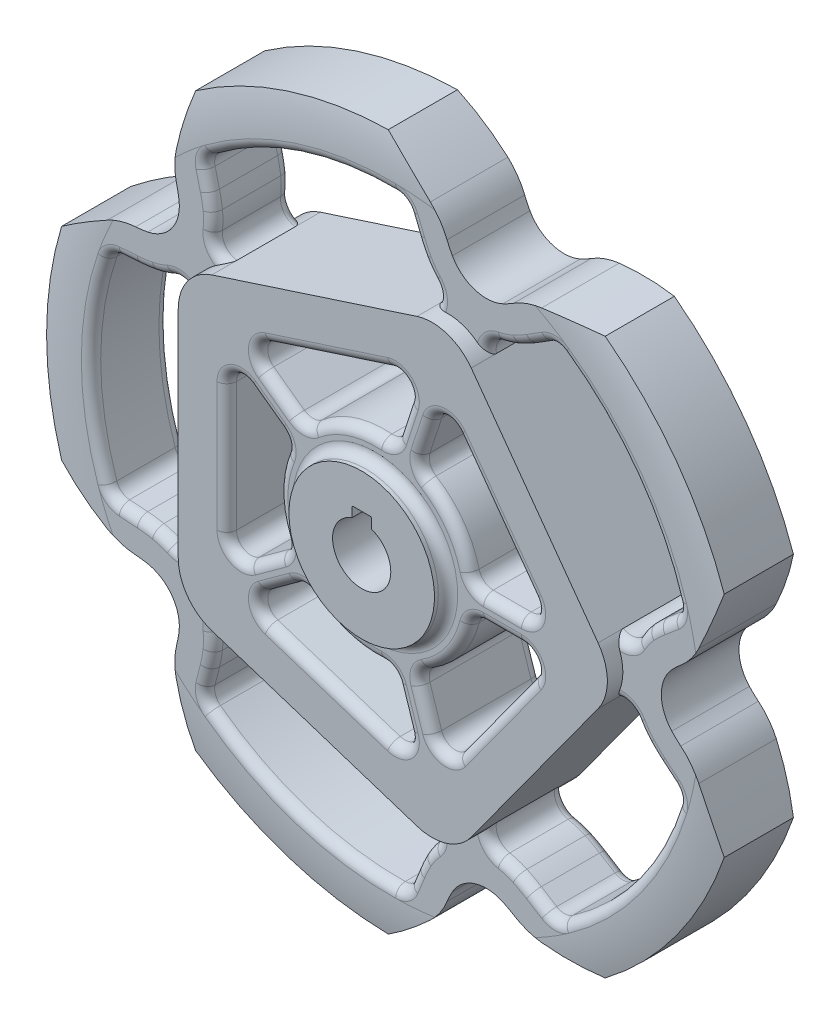
SolidWorks part; units mm, degrees
note: '?' marks a value the reader was unsure of.
material "7075-O (SS)"
ref_plane "Front Plane" through (0, 0, 0) normal (0, 0, 1) x (1, 0, 0)
ref_plane "Top Plane" through (0, 0, 0) normal (0, 1, 0) x (1, 0, 0)
ref_plane "Right Plane" through (0, 0, 0) normal (1, 0, 0) x (0, 0, -1)
sketch "Sketch1" plane through (0, 0, 0) normal (0, 0, 1) x (1, 0, 0)
  line L0 (0, 0) -> (71.6379, 52.048) construction
  line L1 (63.7988, 0) -> (19.7149, 60.6763) construction
  line L2 (19.7149, 60.6763) -> (-51.6143, 37.5) construction
  line L3 (-51.6143, 37.5) -> (-51.6143, -37.5) construction
  line L4 (-51.6143, -37.5) -> (19.7149, -60.6763) construction
  line L5 (19.7149, -60.6763) -> (63.7988, 0) construction
  line L6 (0, 0) -> (55.771, 0) construction
  circle A0 centre (0, 0) radius 63.7988 construction
  arc A1 (57.9284, 5.4759) -> (55.771, 0) centre (63.7988, 0) ccw
  arc A2 (59.7671, 7.2201) -> (57.9284, 5.4759) centre (73.1003, -8.6765) ccw
  arc A3 (59.7671, 7.2201) -> (63.4812, 12.0599) centre (50.7168, 18.0103) ccw
  arc A4 (63.4812, 12.0599) -> (71.6379, 52.048) centre (-15.9497, 49.0881) ccw
  circle A5 centre (0, 0) radius 81.3488 construction
  arc A6 (23.1088, 53.4011) -> (17.2342, 53.0413) centre (19.7149, 60.6763) cw
  arc A7 (25.3357, 54.6108) -> (23.1088, 53.4011) centre (14.3374, 72.2037) cw
  arc A8 (25.3357, 54.6108) -> (31.0865, 56.6475) centre (32.8012, 42.6691) cw
  arc A9 (31.0865, 56.6475) -> (71.6379, 52.048) centre (41.7569, -30.3381) cw
  arc A10 (57.9284, -5.4759) -> (55.771, 0) centre (63.7988, 0) cw
  arc A11 (59.7671, -7.2201) -> (57.9284, -5.4759) centre (73.1003, 8.6765) cw
  arc A12 (59.7671, -7.2201) -> (63.4812, -12.0599) centre (50.7168, -18.0103) cw
  arc A13 (63.4812, -12.0599) -> (71.6379, -52.048) centre (-15.9497, -49.0881) cw
  arc A14 (31.0865, -56.6475) -> (71.6379, -52.048) centre (41.7569, 30.3381) ccw
  arc A15 (25.3357, -54.6108) -> (31.0865, -56.6475) centre (32.8012, -42.6691) ccw
  arc A16 (25.3357, -54.6108) -> (23.1088, -53.4011) centre (14.3374, -72.2037) ccw
  arc A17 (23.1088, -53.4011) -> (17.2342, -53.0413) centre (19.7149, -60.6763) ccw
  arc A18 (12.693, -56.7854) -> (17.2342, -53.0413) centre (19.7149, -60.6763) cw
  arc A19 (11.6024, -59.073) -> (12.693, -56.7854) centre (30.841, -66.8413) cw
  arc A20 (11.6024, -59.073) -> (8.1471, -64.1009) centre (-1.4565, -53.8) cw
  arc A21 (8.1471, -64.1009) -> (-27.3633, -84.2155) centre (-51.6143, 0) cw
  arc A22 (-44.2687, -47.07) -> (-27.3633, -84.2155) centre (41.7569, -30.3381) ccw
  arc A23 (-44.1087, -40.9714) -> (-44.2687, -47.07) centre (-30.4446, -44.3812) ccw
  arc A24 (-44.1087, -40.9714) -> (-43.6465, -38.4796) centre (-64.2393, -35.9479) ccw
  arc A25 (-43.6465, -38.4796) -> (-45.1196, -32.7813) centre (-51.6143, -37.5) ccw
  arc A26 (-50.0837, -29.6194) -> (-45.1196, -32.7813) centre (-51.6143, -37.5) cw
  arc A27 (-52.5964, -29.2891) -> (-50.0837, -29.6194) centre (-54.0395, -49.9867) cw
  arc A28 (-52.5964, -29.2891) -> (-58.446, -27.5566) centre (-51.6169, -15.2399) cw
  arc A29 (-58.446, -27.5566) -> (-88.5494, 0) centre (-15.9497, 49.0881) cw
  arc A30 (-58.446, 27.5566) -> (-88.5494, 0) centre (-15.9497, -49.0881) ccw
  arc A31 (-52.5964, 29.2891) -> (-58.446, 27.5566) centre (-51.6169, 15.2399) ccw
  arc A32 (-52.5964, 29.2891) -> (-50.0837, 29.6194) centre (-54.0395, 49.9867) ccw
  arc A33 (-50.0837, 29.6194) -> (-45.1196, 32.7813) centre (-51.6143, 37.5) ccw
  arc A34 (-43.6465, 38.4796) -> (-45.1196, 32.7813) centre (-51.6143, 37.5) cw
  arc A35 (-44.1087, 40.9714) -> (-43.6465, 38.4796) centre (-64.2393, 35.9479) cw
  arc A36 (-44.1087, 40.9714) -> (-44.2687, 47.07) centre (-30.4446, 44.3812) cw
  arc A37 (-44.2687, 47.07) -> (-27.3633, 84.2155) centre (41.7569, 30.3381) cw
  arc A38 (8.1471, 64.1009) -> (-27.3633, 84.2155) centre (-51.6143, 0) ccw
  arc A39 (11.6024, 59.073) -> (8.1471, 64.1009) centre (-1.4565, 53.8) ccw
  arc A40 (11.6024, 59.073) -> (12.693, 56.7854) centre (30.841, 66.8413) ccw
  arc A41 (12.693, 56.7854) -> (17.2342, 53.0413) centre (19.7149, 60.6763) ccw
  point P9 (73.1003, -8.6765)
  point P12 (50.7168, 18.0103)
  point P97 (0, 0)
  dimension "D1" = 16.0557
  dimension "D4" = 162.6976
  dimension "D7" = 5
  dimension "D8" = 127.5976
  dimension "D2" = 8.6765
  dimension "D3" = 9.3015
  dimension "D5" = 13.082
  dimension "D6" = 18.0103
extrude "Boss-Extrude1" add sketch "Sketch1" along normal mid plane 16 contours A41 A40 A39 A38 A37 A36 A35 A34 A33 A32 A31 A30 A29 A28 A27 A26 A25 A24 A23 A22 A21 A20 A19 A18 A17 A16 A15 A14 A13 A12 A11 A10 A1 A2 A3 A4 A9 A8 A7 A6
sketch "Sketch2" plane through (0, 0, 0) normal (0, 0, 1) x (1, 0, 0)
  line L0 (19.7149, 60.6763) -> (0, 0) construction
  circle A0 centre (0, 0) radius 71.8266
  circle A1 centre (19.7149, 60.6763) radius 8.0278 construction
  dimension "D1" = 16.0557
extrude "Cut-Extrude1" cut sketch "Sketch2" along direction (0, 0, 1) on the side of the normal through all both and the other way through all flip side to cut
sketch "Sketch3" plane through (0, 0, 0) normal (0, 1, 0) x (1, 0, 0)
  line L0 (0, 0) -> (0, 8) construction
  line L1 (8.1471, 8) -> (-1.3828, 8) construction
  line L2 (0, 0) -> (-86.9505, 0) construction
  line L3 (0, 8) -> (-63.7988, 8) construction
  line L4 (-1.3828, 8) -> (-41.0921, 8) construction
  line L5 (-63.7988, 8) -> (-86.9505, 8)
  line L6 (-86.9505, 8) -> (-86.9505, -8)
  line L7 (-63.7988, -8) -> (-86.9505, -8)
  arc A0 (-63.7988, 8) -> (-86.9505, 0) centre (-63.7988, -29.5) ccw
  arc A1 (-63.7988, -8) -> (-86.9505, 0) centre (-63.7988, 29.5) cw
  dimension "D2" = 75
  dimension "D1" = 63.7988
revolve "Cut-Revolve1" cut sketch "Sketch3" angle 360 about L0
sketch "Sketch4" plane through (0, 0, 0) normal (0, 0, 1) x (1, 0, 0)
  line L1 (50.2029, 0) -> (15.5135, 47.7458)
  line L2 (15.5135, 47.7458) -> (-40.615, 29.5085)
  line L3 (-40.615, 29.5085) -> (-40.615, -29.5085)
  line L4 (-40.615, -29.5085) -> (15.5135, -47.7458)
  line L5 (15.5135, -47.7458) -> (50.2029, 0)
  circle A0 centre (0, 0) radius 40.615 construction
  dimension "D1" = 81.23
extrude "Boss-Extrude2" add sketch "Sketch4" along normal mid plane 22.4
fillet "Fillet2" radius 10 10 edges at (-40.615, 29.5085, 9.6) (-40.615, -29.5085, 9.6) (15.5135, -47.7458, 9.6) (50.2029, 0, 9.6) (15.5135, 47.7458, 9.6) (-40.615, 29.5085, -9.6) (15.5135, 47.7458, -9.6) (50.2029, 0, -9.6) (15.5135, -47.7458, -9.6) (-40.615, -29.5085, -9.6)
sketch "Sketch5" plane through (0, 0, 0) normal (0, 0, 1) x (1, 0, 0)
  circle A0 centre (0, 0) radius 15
  dimension "D1" = 30
extrude "Boss-Extrude3" add sketch "Sketch5" along normal blind 14
sketch "Sketch6" plane through (0, 0, 0) normal (0, 0, 1) x (1, 0, 0)
  line L5 (-2, 7.8) -> (2, 7.8)
  line L6 (-2, 7.8) -> (-2, 4.2)
  line L7 (-2, 4.2) -> (2, 4.2)
  line L8 (2, 7.8) -> (2, 4.2)
  line L9 (-2, 7.8) -> (2, 4.2) construction
  line L10 (-2, 4.2) -> (2, 7.8) construction
  circle A0 centre (0, 0) radius 6
  point P0 (0, 0)
  point P3 (0, 6)
  dimension "D1" = 12
  dimension "D2" = 4
  dimension "D3" = 3.6
extrude "Cut-Extrude2" cut sketch "Sketch6" against normal through all both and the other way through all contours L6 A0 L8 L7
fillet "Fillet10" radius 0.25 2 edges at (2, 7.8, 1.4) (-2, 7.8, 1.4)
sketch "Sketch7" plane through (0, 0, 0) normal (0, 0, 1) x (1, 0, 0)
  line L0 (19.7841, 41.8679) -> (45.9324, 5.8779)
  line L1 (45.9324, -5.8779) -> (19.7841, -41.8679)
  line L2 (8.6037, -45.5007) -> (-33.7052, -31.7537)
  line L4 (-33.7052, 31.7537) -> (8.6037, 45.5007) construction
  line L9 (-33.7052, 31.7537) -> (8.6037, 45.5007)
  line L10 (-12.5507, 38.6272) -> (-19.0969, 58.7742) construction
  line L11 (-40.615, -22.2431) -> (-40.615, 22.2431)
  arc A3 (8.6037, 45.5007) -> (8.7547, 50.3947) centre (6.2268, 48.0233) ccw
  arc A4 (8.7547, 50.3947) -> (6.5701, 53.3927) centre (19.7149, 60.6763) cw
  arc A10 (0.9777, 61.7911) -> (-37.1108, 49.4153) centre (0, 0) ccw
  arc A11 (-38.2205, 46.2921) -> (-37.1108, 49.4153) centre (-35.3093, 47.0165) cw
  arc A12 (5.1115, 56.4521) -> (3.7112, 59.9166) centre (-5093.1659, -2002.1636) ccw
  arc A13 (6.5701, 53.3927) -> (5.1115, 56.4521) centre (30.841, 66.8413) cw
  arc A15 (3.7112, 59.9166) -> (0.9777, 61.7911) centre (0.9302, 58.7914) ccw
  arc A16 (-36.704, 35.6243) -> (-36.6988, 39.3337) centre (-51.6143, 37.5) ccw
  arc A17 (45.9324, 5.8779) -> (50.6336, 7.2466) centre (47.5971, 8.918) ccw
  arc A18 (50.6336, 7.2466) -> (52.8097, 10.2507) centre (63.7988, 0) cw
  arc A19 (52.8097, 10.2507) -> (55.2687, 12.5833) centre (73.1003, -8.6765) cw
  arc A20 (55.2687, 12.5833) -> (58.1309, 14.9856) centre (-3478.0456, 4225.1861) ccw
  arc A21 (58.1309, 14.9856) -> (59.0689, 18.1646) centre (56.2014, 17.2829) ccw
  arc A22 (59.0689, 18.1646) -> (35.5289, 50.5647) centre (0, 0) ccw
  arc A23 (-36.6988, 39.3337) -> (-37.317, 42.6662) centre (-64.2393, 35.9479) ccw
  arc A24 (32.2156, 50.6549) -> (35.5289, 50.5647) centre (33.8042, 48.1101) cw
  arc A25 (29.0464, 48.6752) -> (32.2156, 50.6549) centre (2943.6156, -4613.4722) cw
  arc A26 (26.0681, 47.0574) -> (29.0464, 48.6752) centre (14.3374, 72.2037) ccw
  arc A27 (22.5386, 45.9161) -> (26.0681, 47.0574) centre (19.7149, 60.6763) ccw
  arc A28 (19.7841, 41.8679) -> (22.5386, 45.9161) centre (23.1898, 42.5117) cw
  arc A29 (-37.317, 42.6662) -> (-38.2205, 46.2921) centre (5297.3, 1373.9034) cw
  arc A30 (19.7841, -41.8679) -> (22.5386, -45.9161) centre (23.1898, -42.5117) ccw
  arc A31 (22.5386, -45.9161) -> (26.0681, -47.0574) centre (19.7149, -60.6763) cw
  arc A32 (26.0681, -47.0574) -> (29.0464, -48.6752) centre (14.3374, -72.2037) cw
  arc A33 (29.0464, -48.6752) -> (32.2156, -50.6549) centre (2943.6156, 4613.4722) ccw
  arc A34 (32.2156, -50.6549) -> (35.5289, -50.5647) centre (33.8042, -48.1101) ccw
  arc A35 (35.5289, -50.5647) -> (59.0689, -18.1646) centre (0, 0) ccw
  arc A36 (58.1309, -14.9856) -> (59.0689, -18.1646) centre (56.2014, -17.2829) cw
  arc A37 (55.2687, -12.5833) -> (58.1309, -14.9856) centre (-3478.0456, -4225.1861) cw
  arc A39 (52.8097, -10.2507) -> (55.2687, -12.5833) centre (73.1003, 8.6765) ccw
  arc A40 (50.6336, -7.2466) -> (52.8097, -10.2507) centre (63.7988, 0) ccw
  arc A41 (45.9324, -5.8779) -> (50.6336, -7.2466) centre (47.5971, -8.918) cw
  arc A43 (-33.7052, -31.7537) -> (-36.704, -35.6243) centre (-33.265, -35.1917) ccw
  arc A44 (-36.704, -35.6243) -> (-36.6988, -39.3337) centre (-51.6143, -37.5) cw
  arc A45 (-36.6988, -39.3337) -> (-37.317, -42.6662) centre (-64.2393, -35.9479) cw
  arc A46 (-37.317, -42.6662) -> (-38.2205, -46.2921) centre (5297.3, -1373.9034) ccw
  arc A47 (-38.2205, -46.2921) -> (-37.1108, -49.4153) centre (-35.3093, -47.0165) ccw
  arc A48 (-37.1108, -49.4153) -> (0.9777, -61.7911) centre (0, 0) ccw
  arc A49 (3.7112, -59.9166) -> (0.9777, -61.7911) centre (0.9302, -58.7914) cw
  arc A50 (5.1115, -56.4521) -> (3.7112, -59.9166) centre (-5093.1659, 2002.1636) cw
  arc A51 (6.5701, -53.3927) -> (5.1115, -56.4521) centre (30.841, -66.8413) ccw
  arc A52 (8.7547, -50.3947) -> (6.5701, -53.3927) centre (19.7149, -60.6763) ccw
  arc A53 (8.6037, -45.5007) -> (8.7547, -50.3947) centre (6.2268, -48.0233) cw
  arc A54 (-40.615, 22.2431) -> (-45.2229, 23.8991) centre (-43.7487, 20.7621) ccw
  arc A55 (-45.2229, 23.8991) -> (-48.7491, 22.7478) centre (-51.6143, 37.5) cw
  arc A56 (-48.7491, 22.7478) -> (-52.1096, 22.306) centre (-54.0395, 49.9867) cw
  arc A57 (-52.1096, 22.306) -> (-55.8372, 22.0448) centre (330.2959, -5462.5912) ccw
  arc A58 (-55.8372, 22.0448) -> (-58.4647, 20.0243) centre (-55.6265, 19.0523) ccw
  arc A59 (-58.4647, 20.0243) -> (-58.4647, -20.0243) centre (0, 0) ccw
  arc A90 (-55.8372, -22.0448) -> (-58.4647, -20.0243) centre (-55.6265, -19.0523) cw
  arc A91 (-52.1096, -22.306) -> (-55.8372, -22.0448) centre (330.2959, 5462.5912) cw
  arc A92 (-48.7491, -22.7478) -> (-52.1096, -22.306) centre (-54.0395, -49.9867) ccw
  arc A93 (-45.2229, -23.8991) -> (-48.7491, -22.7478) centre (-51.6143, -37.5) ccw
  arc A94 (-33.7052, 31.7537) -> (-36.704, 35.6243) centre (-33.265, 35.1917) cw
  arc A95 (-40.615, -22.2431) -> (-45.2229, -23.8991) centre (-43.7487, -20.7621) cw
  point P120 (0, 0)
  dimension "D5" = 3
  dimension "D1" = 5
extrude "Cut-Extrude5" cut sketch "Sketch7" against normal through all both and the other way through all
sketch "Sketch8" plane through (0, 0, 0) normal (0, 0, 1) x (1, 0, 0)
  line L5 (6.9355, 29.4355) -> (4.5235, 22.0122)
  line L6 (11.6908, 27.8904) -> (9.2788, 20.4671)
  line L7 (32.5651, 7.2634) -> (16.971, 28.7267)
  line L8 (30.138, 2.5) -> (22.3327, 2.5)
  line L9 (30.138, -2.5) -> (22.3327, -2.5)
  line L10 (3.1553, 33.2157) -> (-22.0764, 25.0175)
  line L11 (16.971, -28.7267) -> (32.5651, -7.2634)
  line L12 (11.6908, -27.8904) -> (9.2788, -20.4671)
  line L13 (6.9355, -29.4355) -> (4.5235, -22.0122)
  line L14 (-22.0764, -25.0175) -> (3.1553, -33.2157)
  line L15 (0, 0) -> (-9.4606, 29.1166) construction
  line L16 (0, 0) -> (-30.615, 22.2431) construction
  line L17 (-22.9127, 19.7372) -> (-16.5981, 15.1494)
  line L18 (-22.9127, -19.7372) -> (-16.5981, -15.1494)
  line L19 (-25.8516, -15.6921) -> (-19.537, -11.1043)
  line L20 (-30.615, 13.2651) -> (-30.615, -13.2651)
  line L21 (-25.8516, 15.6921) -> (-19.537, 11.1043)
  arc A0 (-16.5981, 15.1494) -> (-12.8998, 15.2839) centre (-14.8347, 17.5764) ccw
  arc A10 (4.5235, 22.0122) -> (1.4525, 19.9472) centre (1.6704, 22.9393) cw
  arc A11 (3.1553, 33.2157) -> (6.9355, 29.4355) centre (4.0824, 30.3626) cw
  arc A12 (19.4197, 4.7826) -> (10.5496, 16.9914) centre (0, 0) ccw
  arc A14 (9.2788, 20.4671) -> (10.5496, 16.9914) centre (12.132, 19.5401) ccw
  arc A16 (16.971, 28.7267) -> (11.6908, 27.8904) centre (14.544, 26.9634) ccw
  arc A17 (32.5651, 7.2634) -> (30.138, 2.5) centre (30.138, 5.5) cw
  arc A18 (22.3327, 2.5) -> (19.4197, 4.7826) centre (22.3327, 5.5) cw
  arc A19 (10.5496, -16.9914) -> (19.4197, -4.7826) centre (0, 0) ccw
  arc A20 (22.3327, -2.5) -> (19.4197, -4.7826) centre (22.3327, -5.5) ccw
  arc A21 (32.5651, -7.2634) -> (30.138, -2.5) centre (30.138, -5.5) ccw
  arc A22 (16.971, -28.7267) -> (11.6908, -27.8904) centre (14.544, -26.9634) cw
  arc A23 (9.2788, -20.4671) -> (10.5496, -16.9914) centre (12.132, -19.5401) cw
  arc A24 (1.4525, 19.9472) -> (-12.8998, 15.2839) centre (0, 0) ccw
  arc A25 (-22.0764, 25.0175) -> (-22.9127, 19.7372) centre (-21.1494, 22.1643) ccw
  arc A26 (-12.8998, -15.2839) -> (1.4525, -19.9472) centre (0, 0) ccw
  arc A27 (4.5235, -22.0122) -> (1.4525, -19.9472) centre (1.6704, -22.9393) ccw
  arc A28 (3.1553, -33.2157) -> (6.9355, -29.4355) centre (4.0824, -30.3626) ccw
  arc A29 (-22.0764, -25.0175) -> (-22.9127, -19.7372) centre (-21.1494, -22.1643) cw
  arc A30 (-16.5981, -15.1494) -> (-12.8998, -15.2839) centre (-14.8347, -17.5764) cw
  arc A31 (-18.5221, 7.5454) -> (-18.5221, -7.5454) centre (0, 0) ccw
  arc A32 (-19.537, -11.1043) -> (-18.5221, -7.5454) centre (-21.3004, -8.6772) ccw
  arc A33 (-30.615, -13.2651) -> (-25.8516, -15.6921) centre (-27.615, -13.2651) ccw
  arc A34 (-30.615, 13.2651) -> (-25.8516, 15.6921) centre (-27.615, 13.2651) cw
  arc A35 (-19.537, 11.1043) -> (-18.5221, 7.5454) centre (-21.3004, 8.6772) cw
  point P67 (0, 0)
  dimension "D3" = 40
  dimension "D4" = 3
  dimension "D5" = 3
  dimension "D2" = 5
  dimension "D1" = 5
extrude "Cut-Extrude6" cut sketch "Sketch8" against normal through all both and the other way through all
fillet "Fillet7" radius 2 80 edges at (6.2037, 32.4839, -11.2) (5.7295, 25.7239, -11.2) (3.3444, 20.4497, -11.2) (-6.1803, 19.0211, -11.2) (-14.7257, 14.5784, -11.2) (-19.7554, 17.4433, -11.2) (-24.1124, 22.6336, -11.2) (-28.977, 15.9381, -11.2) (-22.6943, 13.3982, -11.2) (-18.4154, 9.5, -11.2) (-20, 0, -11.2) (-18.4154, -9.5, -11.2) (-22.6943, -13.3982, -11.2) (-28.977, -15.9381, -11.2) (-24.1124, -22.6336, -11.2) (-19.7554, -17.4433, -11.2) (-14.7257, -14.5784, -11.2) (-6.1803, -19.0211, -11.2) (3.3444, -20.4497, -11.2) (5.7295, -25.7239, -11.2) (6.2037, -32.4839, -11.2) (14.0747, -29.9264, -11.2) (10.4848, -24.1788, -11.2) (9.3144, -18.51, -11.2) (16.1803, -11.7557, -11.2) (20.4823, -3.1386, -11.2) (26.2354, -2.5, -11.2) (32.8111, -4.138, -11.2) (32.8111, 4.138, -11.2) (26.2354, 2.5, -11.2) (20.4823, 3.1386, -11.2) (16.1803, 11.7557, -11.2) (9.3144, 18.51, -11.2) (10.4848, 24.1788, -11.2) (14.0747, 29.9264, -11.2) (14.0747, -29.9264, 11.2) (10.4848, -24.1788, 11.2) (9.3144, -18.51, 11.2) (16.1803, -11.7557, 11.2) (20.4823, -3.1386, 11.2) (26.2354, -2.5, 11.2) (32.8111, -4.138, 11.2) (32.8111, 4.138, 11.2) (26.2354, 2.5, 11.2) (20.4823, 3.1386, 11.2) (16.1803, 11.7557, 11.2) (9.3144, 18.51, 11.2) (10.4848, 24.1788, 11.2) (14.0747, 29.9264, 11.2) (-24.1124, -22.6336, 11.2) (-19.7554, -17.4433, 11.2) (-14.7257, -14.5784, 11.2) (-6.1803, -19.0211, 11.2) (3.3444, -20.4497, 11.2) (5.7295, -25.7239, 11.2) (6.2037, -32.4839, 11.2) (-28.977, 15.9381, 11.2) (-22.6943, 13.3982, 11.2) (-18.4154, 9.5, 11.2) (-20, 0, 11.2) (-18.4154, -9.5, 11.2) (-22.6943, -13.3982, 11.2) (-28.977, -15.9381, 11.2) (6.2037, 32.4839, 11.2) (5.7295, 25.7239, 11.2) (3.3444, 20.4497, 11.2) (-6.1803, 19.0211, 11.2) (-14.7257, 14.5784, 11.2) (-19.7554, 17.4433, 11.2) (-24.1124, 22.6336, 11.2) (-9.4606, 29.1166, -11.2) (-30.615, 0, -11.2) (-9.4606, -29.1166, -11.2) (24.7681, -17.995, -11.2) (24.7681, 17.995, -11.2) (24.7681, -17.995, 11.2) (24.7681, 17.995, 11.2) (-9.4606, -29.1166, 11.2) (-30.615, 0, 11.2) (-9.4606, 29.1166, 11.2)
fillet "Fillet8" radius 2 1 edges at (15, 0, 11.2)
fillet "Fillet9" radius 2 110 edges at (48.566, 5.5901, -8) (51.6286, 8.816, -8) (54.0035, 11.4546, -8) (56.7, 13.7842, -8) (59.0788, 16.4338, -8) (20.3242, 44.4616, -8) (24.3387, 46.3774, -8) (27.582, 47.8208, -8) (30.6308, 49.6653, -8) (33.8859, 51.1089, -8) (9.6912, 47.9165, -8) (7.5696, 51.826, -8) (5.7941, 54.9001, -8) (4.4117, 58.1845, -8) (2.6268, 61.2656, -8) (-36.005, 33.0689, -8) (-36.5865, 37.4788, -8) (-36.957, 41.0094, -8) (-37.7691, 44.4791, -8) (-38.1362, 48.0209, -8) (-42.5765, 24.0239, -8) (-46.9503, 23.2142, -8) (-50.4226, 22.4756, -8) (-53.9734, 22.1757, -8) (-57.4553, 21.4304, -8) (-42.5765, -24.0239, -8) (-46.9503, -23.2142, -8) (-50.4226, -22.4756, -8) (-53.9734, -22.1757, -8) (-57.4553, -21.4304, -8) (20.3242, -44.4616, -8) (24.3387, -46.3774, -8) (27.582, -47.8208, -8) (30.6308, -49.6653, -8) (33.8859, -51.1089, -8) (48.566, -5.5901, -8) (51.6286, -8.816, -8) (54.0035, -11.4546, -8) (56.7, -13.7842, -8) (59.0788, -16.4338, -8) (-36.005, -33.0689, -8) (-36.5865, -37.4788, -8) (-36.957, -41.0094, -8) (-37.7691, -44.4791, -8) (-38.1362, -48.0209, -8) (9.6912, -47.9165, -8) (7.5696, -51.826, -8) (5.7941, -54.9001, -8) (4.4117, -58.1845, -8) (2.6268, -61.2656, -8) (-36.005, -33.0689, 8) (-36.5865, -37.4788, 8) (-36.957, -41.0094, 8) (-37.7691, -44.4791, 8) (-38.1362, -48.0209, 8) (9.6912, -47.9165, 8) (7.5696, -51.826, 8) (5.7941, -54.9001, 8) (4.4117, -58.1845, 8) (2.6268, -61.2656, 8) (20.3242, -44.4616, 8) (24.3387, -46.3774, 8) (27.582, -47.8208, 8) (30.6308, -49.6653, 8) (33.8859, -51.1089, 8) (48.566, -5.5901, 8) (51.6286, -8.816, 8) (54.0035, -11.4546, 8) (56.7, -13.7842, 8) (59.0788, -16.4338, 8) (48.566, 5.5901, 8) (51.6286, 8.816, 8) (54.0035, 11.4546, 8) (56.7, 13.7842, 8) (59.0788, 16.4338, 8) (20.3242, 44.4616, 8) (24.3387, 46.3774, 8) (27.582, 47.8208, 8) (30.6308, 49.6653, 8) (33.8859, 51.1089, 8) (-42.5765, 24.0239, 8) (-46.9503, 23.2142, 8) (-50.4226, 22.4756, 8) (-53.9734, 22.1757, 8) (-57.4553, 21.4304, 8) (-42.5765, -24.0239, 8) (-46.9503, -23.2142, 8) (-50.4226, -22.4756, 8) (-53.9734, -22.1757, 8) (-57.4553, -21.4304, 8) (9.6912, 47.9165, 8) (7.5696, 51.826, 8) (5.7941, 54.9001, 8) (4.4117, 58.1845, 8) (2.6268, 61.2656, 8) (-36.005, 33.0689, 8) (-36.5865, 37.4788, 8) (-36.957, 41.0094, 8) (-37.7691, 44.4791, 8) (-38.1362, 48.0209, 8) (49.9963, 36.3244, -8) (-19.0969, 58.7742, -8) (-61.7988, 0, -8) (49.9963, -36.3244, -8) (-19.0969, -58.7742, -8) (-19.0969, -58.7742, 8) (49.9963, -36.3244, 8) (49.9963, 36.3244, 8) (-61.7988, 0, 8) (-19.0969, 58.7742, 8)
ref_axis "Axis1" through (0, 0, -11.2) along (0, 0, 1)?
